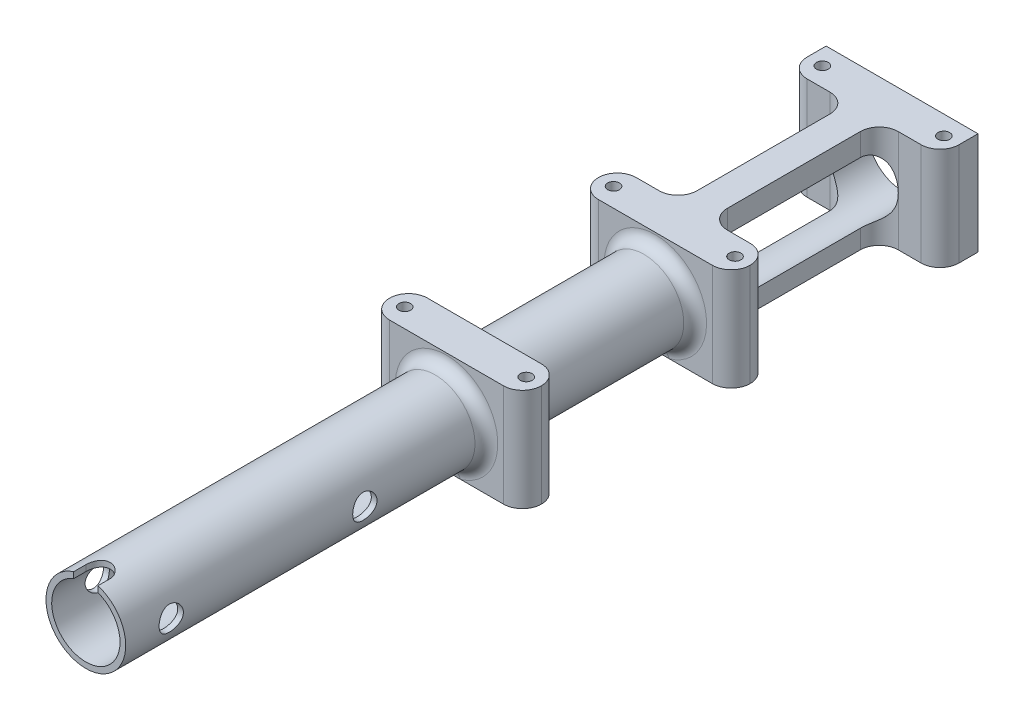
SolidWorks part; units mm, degrees
material "6063-T6"
ref_plane "Front Plane" through (0, 0, 0) normal (0, 0, 1) x (1, 0, 0)
ref_plane "Top Plane" through (0, 0, 0) normal (0, 1, 0) x (1, 0, 0)
ref_plane "Right Plane" through (0, 0, 0) normal (1, 0, 0) x (0, 0, -1)
sketch "Sketch1" plane through (0, 0, 0) normal (0, 0, 1) x (1, 0, 0)
  circle A1 centre (0, 0) radius 10.5
  dimension "D1" = 21
extrude "Boss-Extrude1" add sketch "Sketch1" along normal blind 150
sketch "Sketch3" plane through (0, 0, 0) normal (0, 1, 0) x (1, 0, 0)
  line L0 (0, 0) -> (0, 101.6874) construction
  line L1 (0, 0) -> (-109.3194, 0) construction
  line L2 (20, 0) -> (-20, 0)
  line L3 (-20, 0) -> (-20, 10)
  line L4 (-20, 10) -> (-4, 10)
  line L5 (-4, 10) -> (-4, 55)
  line L6 (-4, 55) -> (-20, 55)
  line L7 (-20, 55) -> (-20, 65)
  line L8 (-20, 65) -> (20, 65)
  line L9 (20, 55) -> (20, 65)
  line L10 (4, 55) -> (20, 55)
  line L11 (4, 10) -> (4, 55)
  line L12 (20, 10) -> (4, 10)
  line L13 (20, 0) -> (20, 10)
  line L14 (-20, 5) -> (36.7917, 5) construction
  line L15 (-20, 60) -> (21.8388, 60) construction
  line L17 (12, -45) -> (-20, -45) construction
  line L24 (0, -50.1148) -> (0, -24.3835) construction
  line L28 (-20, -55) -> (20, -55)
  line L29 (-20, -55) -> (-20, -45)
  line L30 (-20, -45) -> (20, -45)
  line L31 (20, -55) -> (20, -45)
  line L32 (-20, -55) -> (20, -45) construction
  line L33 (-20, -45) -> (20, -55) construction
  circle A0 centre (-16, 5) radius 1.55
  circle A1 centre (16, 5) radius 1.55
  circle A4 centre (-16, 60) radius 1.55
  circle A5 centre (16, 60) radius 1.55
  circle A6 centre (16, -50) radius 1.55
  circle A7 centre (-16, -50) radius 1.55
  point P12 (0, 65)
  point P29 (0, -36.7499)
  point P30 (0, -36.7499)
  point P33 (0, -40.32)
  dimension "D6" = 3.1
  dimension "D8" = 3.1
  dimension "D11" = 32
  dimension "D12" = 55
  dimension "D13" = 32
  dimension "D2" = 45
  dimension "D3" = 10
  dimension "D4" = 10
  dimension "D5" = 8
  dimension "D7" = 4
  dimension "D9" = 5
  dimension "D10" = 40
  dimension "D14" = 40
  dimension "D15" = 45
  dimension "D16" = 10
  dimension "D17" = 40
extrude "Boss-Extrude2" add sketch "Sketch3" along normal blind 14 and the other way blind 13
sketch "Sketch6" plane through (0, 0, 0) normal (0, 0, 1) x (1, 0, 0)
  circle A0 centre (0, 0) radius 9
  dimension "D1" = 18
extrude "Cut-Extrude1" cut sketch "Sketch6" against normal through all both and the other way through all
sketch "Sketch7" plane through (0, 0, 0) normal (1, 0, 0) x (0, 0, -1)
  line L0 (-150, 9) -> (-150, -9) construction
  circle A0 centre (-87, 0) radius 3.2
  circle A1 centre (-138, 0) radius 3.2
  dimension "D1" = 6.4
  dimension "D2" = 12
  dimension "D3" = 63
extrude "Cut-Extrude2" cut sketch "Sketch7" against normal through all both and the other way through all
sketch "Sketch8" plane through (0, 0, 0) normal (0, 1, 0) x (1, 0, 0)
  line L0 (0, 0) -> (0, -186.8535) construction
  line L1 (3.2, -150) -> (-3.2, -150)
  line L2 (-3.2, -150) -> (-3.2, -146.8)
  line L3 (3.2, -150) -> (3.2, -146.8)
  line L4 (-10.5, -150) -> (10.5, -150) construction
  arc A0 (-3.2, -146.8) -> (3.2, -146.8) centre (0, -146.8) cw
  point P9 (0, -150)
  dimension "D1" = 3.2
  dimension "D2" = 3.2
extrude "Cut-Extrude3" cut sketch "Sketch8" along normal through all
fillet "Fillet1" radius 5 14 edges at (-4, 11.0311, -55) (4, 11.0311, -55) (-4, 11.0311, -10) (4, 11.0311, -10) (-4, -10.5311, -55) (4, -10.5311, -55) (4, -10.5311, -10) (-4, -10.5311, -10) (-20, 0.5, -10) (-20, 0.5, 0) (-20, 0.5, -55) (20, 0.5, -55) (20, 0.5, -10) (20, 0.5, 0)
fillet "Fillet3" radius 3 1 edges at (10.5, 0, 0)
fillet "圆角1" radius 5 4 edges at (20, 0.5, 55) (20, 0.5, 45) (-20, 0.5, 55) (-20, 0.5, 45)
fillet "圆角2" radius 3 2 edges at (10.5, 0, 55) (-10.5, 0, 45)
